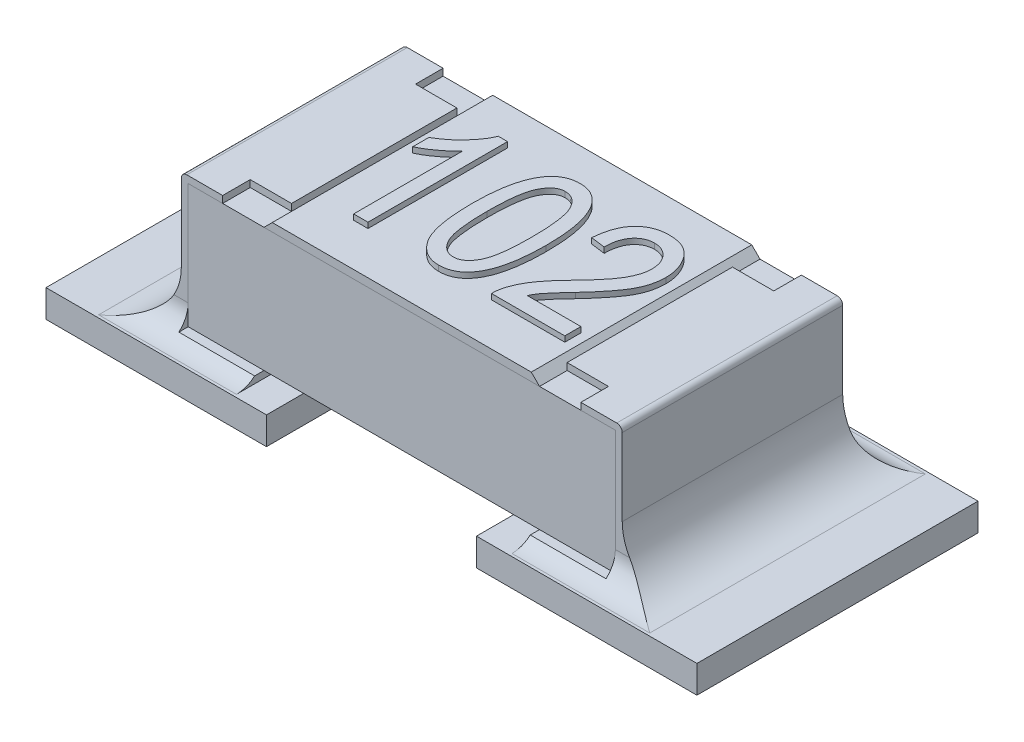
SolidWorks part; units mm, degrees
material "Ceramic Porcelain"
ref_plane "Front Plane" through (0, 0, 0) normal (0, 0, 1) x (1, 0, 0)
ref_plane "Top Plane" through (0, 0, 0) normal (0, 1, 0) x (1, 0, 0)
ref_plane "Right Plane" through (0, 0, 0) normal (1, 0, 0) x (0, 0, -1)
sketch "Sketch1" plane through (0, 0, 0) normal (1, 0, 0) x (0, 0, -1)
  line L0 (0, 55) -> (0, -55) construction
  line L1 (-0.4, 0.575) -> (0.4, 0.575)
  line L2 (-0.4, 0.575) -> (-0.4, 0.125)
  line L3 (-0.4, 0.125) -> (0.4, 0.125)
  line L4 (0.4, 0.575) -> (0.4, 0.125)
  line L5 (55, 0) -> (-55, 0) construction
  dimension "D1" = 0.8
  dimension "D2" = 0.4
  dimension "D3" = 0.45
  dimension "D4" = 0.125
extrude "Boss-Extrude1" add sketch "Sketch1" along normal mid plane 1.55
sketch "Sketch2" plane through (0, 0, 0) normal (0, 0, 1) x (1, 0, 0)
  line L0 (-0.5, 0.6) -> (-0.78, 0.6)
  line L1 (-0.8, 0.58) -> (-0.8, 0.1)
  line L2 (-0.8, 0.1) -> (-0.5, 0.1)
  line L3 (-0.5, 0.1) -> (-0.5, 0.125)
  line L4 (0.775, 0.125) -> (-0.775, 0.125) construction
  line L5 (-0.5, 0.125) -> (-0.775, 0.125)
  line L6 (-0.775, 0.125) -> (-0.775, 0.575)
  line L7 (-0.775, 0.575) -> (-0.5, 0.575)
  line L8 (0.775, 0.575) -> (-0.775, 0.575) construction
  line L9 (-0.5, 0.575) -> (-0.5, 0.6)
  line L11 (0.5, 0.575) -> (0.5, 0.6)
  line L12 (0.5, 0.6) -> (0.78, 0.6)
  line L13 (0.8, 0.58) -> (0.8, 0.1)
  line L14 (0.8, 0.1) -> (0.5, 0.1)
  line L15 (0.5, 0.1) -> (0.5, 0.125)
  line L16 (0.5, 0.125) -> (0.775, 0.125)
  line L17 (0.775, 0.125) -> (0.775, 0.575)
  line L18 (0.775, 0.575) -> (0.5, 0.575)
  arc A0 (0.78, 0.6) -> (0.8, 0.58) centre (0.78, 0.58) cw
  arc A1 (-0.78, 0.6) -> (-0.8, 0.58) centre (-0.78, 0.58) ccw
  point P28 (-0.8, 0.6)
  dimension "D6" = 0.02
  dimension "D1" = 0.025
  dimension "D2" = 0.025
  dimension "D3" = 0.025
  dimension "D4" = 0.3
  dimension "D5" = 0.3
extrude "Boss-Extrude2" add sketch "Sketch2" along normal mid plane 0.8 separate body
sketch "Sketch3" plane through (0, 0.6, 0) normal (0, 1, 0) x (1, 0, 0)
  line L0 (0.5, -0.4) -> (0.5, 0.4) construction
  line L1 (-0.5, 0.4) -> (-0.65, 0.4)
  line L2 (-0.5, 0.4) -> (-0.5, 0.3)
  line L3 (-0.5, 0.3) -> (-0.65, 0.3)
  line L4 (-0.65, 0.4) -> (-0.65, 0.3)
  line L5 (-0.5, -0.4) -> (-0.65, -0.4)
  line L6 (-0.5, -0.4) -> (-0.5, -0.3)
  line L7 (-0.5, -0.3) -> (-0.65, -0.3)
  line L8 (-0.65, -0.4) -> (-0.65, -0.3)
  line L9 (0.5, -0.4) -> (0.65, -0.4)
  line L10 (0.5, -0.4) -> (0.5, -0.3)
  line L11 (0.5, -0.3) -> (0.65, -0.3)
  line L12 (0.65, -0.4) -> (0.65, -0.3)
  line L13 (0.775, -0.4) -> (-0.775, -0.4) construction
  line L15 (0.5, 0.4) -> (0.65, 0.4)
  line L16 (0.5, 0.4) -> (0.5, 0.3)
  line L17 (0.5, 0.3) -> (0.65, 0.3)
  line L18 (0.65, 0.4) -> (0.65, 0.3)
  dimension "D1" = 0.15
  dimension "D2" = 0.1
extrude "Cut-Extrude1" cut sketch "Sketch3" against normal blind 0.025
sketch "Sketch4" plane through (0, 0, 0) normal (0, 0, 1) x (1, 0, 0)
  line L0 (-0.5, 0.575) -> (0.5, 0.575)
  line L1 (0.5, 0.575) -> (0.47, 0.605)
  line L2 (0.47, 0.605) -> (-0.47, 0.605)
  line L3 (-0.47, 0.605) -> (-0.5, 0.575)
  dimension "D1" = 45
  dimension "D2" = 45
  dimension "D3" = 0.03
extrude "Boss-Extrude3" add sketch "Sketch4" along normal mid plane 0.8 separate body
sketch "Sketch7" plane through (0, 0, 0) normal (0, 1, 0) x (1, 0, 0)
  line L0 (0, -0.2833) -> (0, 0.2833) construction
  line L1 (-0.381, -0.51) -> (-1.181, -0.51)
  line L2 (-0.381, -0.51) -> (-0.381, 0.51)
  line L3 (-0.381, 0.51) -> (-1.181, 0.51)
  line L4 (-1.181, -0.51) -> (-1.181, 0.51)
  line L5 (0.381, -0.51) -> (1.181, -0.51)
  line L6 (0.381, -0.51) -> (0.381, 0.51)
  line L7 (0.381, 0.51) -> (1.181, 0.51)
  line L8 (1.181, -0.51) -> (1.181, 0.51)
  line L9 (-0.2833, 0) -> (0.2833, 0) construction
  dimension "D1" = 0.8
  dimension "D2" = 0.381
  dimension "D3" = 0.381
  dimension "D4" = 1.02
  dimension "D5" = 0.51
extrude "Boss-Extrude5" add sketch "Sketch7" along normal blind 0.1
fillet "Fillet3" radius 0.2 1 edges at (-0.8, 0.1, 0)
fillet "Fillet4" radius 0.2 1 edges at (0.8, 0.1, 0)
fillet "Fillet5" radius 0.1 2 edges at (0.75, 0.1, -0.4) (0.75, 0.1, 0.4)
fillet "Fillet6" radius 0.1 2 edges at (-0.75, 0.1, 0.4) (-0.75, 0.1, -0.4)
sketch "Esquisse2" plane through (0, 0.605, 0) normal (0, 1, 0) x (1, 0, 0)
  text T0 "102" font "Arial Narrow" height 0.5
extrude "Boss.-Extru.1" add sketch "Esquisse2" along normal blind 0.02
